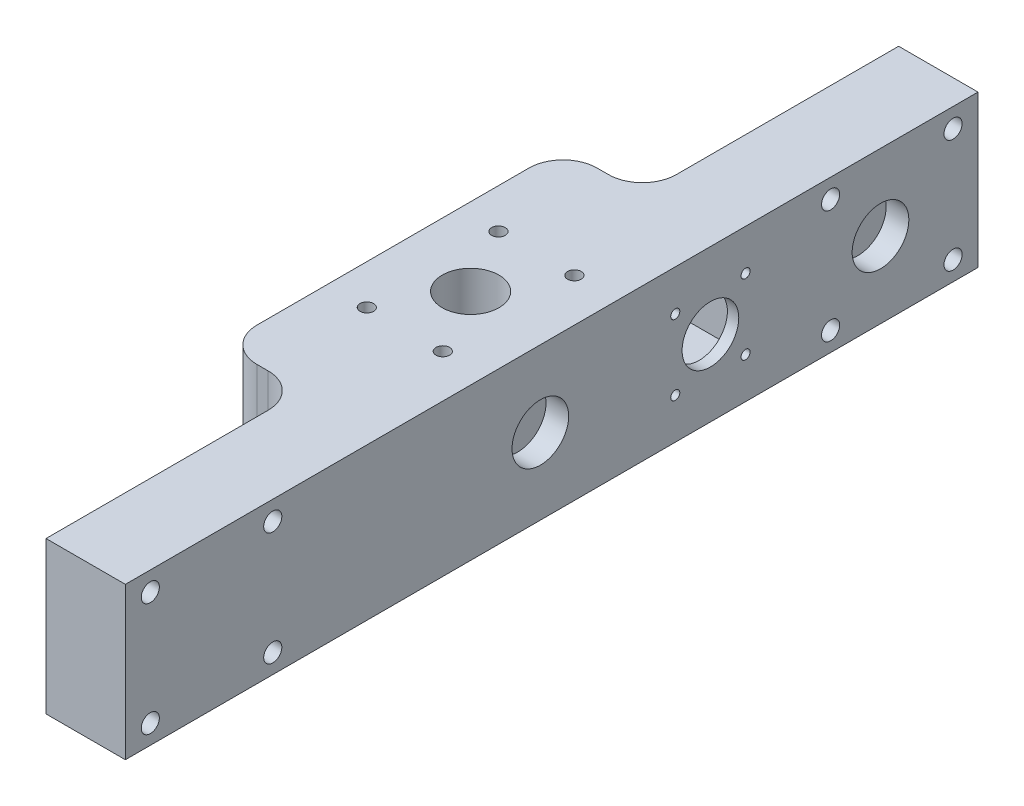
SolidWorks part; units mm, degrees
material "6061-T6 (SS)"
ref_plane "Front" through (0, 0, 0) normal (0, 0, 1) x (1, 0, 0)
ref_plane "Top" through (0, 0, 0) normal (0, 1, 0) x (1, 0, 0)
ref_plane "Right" through (0, 0, 0) normal (1, 0, 0) x (0, 0, -1)
sketch "Sketch1" plane through (0, 0, 0) normal (0, 1, 0) x (1, 0, 0)
  line L0 (0.75, -188) -> (35.75, -188)
  line L1 (0.75, -188) -> (0.75, -75)
  line L2 (0.75, 188) -> (35.75, 188)
  line L3 (35.75, -188) -> (35.75, 188)
  line L4 (-34.25, 75) -> (0.75, 75)
  line L5 (-34.25, 75) -> (-34.25, -75)
  line L6 (-34.25, -75) -> (0.75, -75)
  line L7 (-34.25, 0) -> (0, 0) construction
  line L8 (0.75, 75) -> (0.75, 188)
  line L9 (-16.75, -29.0119) -> (16.75, -29.0119) construction
  line L10 (-16.75, -29.0119) -> (-16.75, 29.0119) construction
  line L11 (-16.75, 29.0119) -> (16.75, 29.0119) construction
  line L12 (16.75, -29.0119) -> (16.75, 29.0119) construction
  line L13 (-16.75, -29.0119) -> (16.75, 29.0119) construction
  line L14 (-16.75, 29.0119) -> (16.75, -29.0119) construction
  circle A0 centre (0, 0) radius 12.5
  circle A1 centre (-16.75, -29.0119) radius 3
  circle A2 centre (16.75, -29.0119) radius 3
  circle A3 centre (16.75, 29.0119) radius 3
  circle A4 centre (-16.75, 29.0119) radius 3
  point P10 (0, 0)
  dimension "D8" = 25
  dimension "D11" = 6
  dimension "D1" = 35
  dimension "D2" = 35
  dimension "D3" = 150
  dimension "D4" = 70
  dimension "D5" = 34.25
  dimension "D6" = 376
  dimension "D7" = 188
  dimension "D9" = 58.0237
  dimension "D10" = 33.5
extrude "Boss-Extrude1" add sketch "Sketch1" along normal blind 67
sketch "Sketch2" plane through (35.75, 0, 0) normal (1, 0, 0) x (0, 0, -1)
  line L0 (-177, 8.5) -> (-123, 8.5) construction
  line L1 (-177, 8.5) -> (-177, 58.5) construction
  line L2 (-177, 58.5) -> (-123, 58.5) construction
  line L3 (-123, 8.5) -> (-123, 58.5) construction
  line L4 (-112, 67) -> (-188, 67) construction
  line L5 (-112, 67) -> (-112, 0) construction
  line L6 (-112, 0) -> (-188, 0) construction
  line L7 (-188, 67) -> (-188, 0) construction
  line L8 (-112, 67) -> (-188, 0) construction
  line L9 (-112, 0) -> (-188, 67) construction
  line L10 (-177, 8.5) -> (-123, 58.5) construction
  line L11 (-177, 58.5) -> (-123, 8.5) construction
  line L12 (-188, 0) -> (188, 0) construction
  line L13 (-188, 67) -> (-188, 0) construction
  line L14 (0, 0) -> (0, 67) construction
  line L15 (-188, 67) -> (188, 67) construction
  circle A0 centre (-177, 58.5) radius 4
  circle A1 centre (-123, 58.5) radius 4
  circle A2 centre (-177, 8.5) radius 4
  circle A3 centre (-123, 8.5) radius 4
  circle A4 centre (177, 58.5) radius 4
  circle A5 centre (177, 8.5) radius 4
  circle A6 centre (123, 8.5) radius 4
  circle A7 centre (123, 58.5) radius 4
  point P4 (-150, 33.5)
  point P9 (-150, 33.5)
  point P32 (0, 33.5)
  dimension "D5" = 8
  dimension "D1" = 50
  dimension "D2" = 54
  dimension "D3" = 76
  dimension "D4" = 67
extrude "Cut-Extrude1" cut sketch "Sketch2" against normal through all
fillet "Fillet1" radius 15 4 edges at (-34.25, 33.5, 75) (-34.25, 33.5, -75) (0.75, 33.5, -75) (0.75, 33.5, 75)
sketch "Sketch3" plane through (35.75, 0, 0) normal (1, 0, 0) x (0, 0, -1)
  line L0 (54.5, 18) -> (85.5, 18) construction
  line L1 (92.5, 11) -> (47.5, 11)
  line L2 (92.5, 11) -> (92.5, 56)
  line L3 (92.5, 56) -> (47.5, 56)
  line L4 (47.5, 11) -> (47.5, 56)
  line L5 (92.5, 11) -> (47.5, 56) construction
  line L6 (92.5, 56) -> (47.5, 11) construction
  line L12 (54.5, 18) -> (54.5, 49) construction
  line L13 (54.5, 49) -> (85.5, 49) construction
  line L14 (85.5, 18) -> (85.5, 49) construction
  line L15 (54.5, 18) -> (85.5, 49) construction
  line L16 (54.5, 49) -> (85.5, 18) construction
  line L17 (0, 0) -> (0, 67) construction
  line L18 (-188, 67) -> (188, 67) construction
  line L19 (0, 33.5) -> (70, 33.5) construction
  line L20 (-5, 33.5) -> (145, 33.5) construction
  circle A0 centre (54.5, 49) radius 2
  circle A1 centre (54.5, 18) radius 2
  circle A2 centre (85.5, 18) radius 2
  circle A3 centre (85.5, 49) radius 2
  circle A4 centre (-5, 33.5) radius 12.5
  circle A5 centre (145, 33.5) radius 12.5
  circle A6 centre (70, 33.5) radius 12.5
  point P0 (70, 33.5)
  point P5 (70, 33.5)
  point P6 (70, 33.5)
  point P25 (70, 33.5)
  dimension "D4" = 4
  dimension "D5" = 70
  dimension "D7" = 25
  dimension "D8" = 25
  dimension "D1" = 31
  dimension "D2" = 31
  dimension "D3" = 45
  dimension "D6" = 150
extrude "Cut-Extrude3" cut sketch "Sketch3" against normal up to surface (70 mm away) from offset 5 contours L4 L1 L2 L3 A3 A2 A1 A0 region at (35.75, 11.6364, -70) up to face at (-34.25, 33.5, 0) offset against normal yes
extrude "Cut-Extrude4" cut sketch "Sketch3<2>" against normal through all contours A0 | A3 | A2 | A1 | A6 region at (35.75, 49, -54.5) region at (35.75, 18, -54.5) region at (35.75, 18, -85.5) region at (35.75, 49, -85.5) region at (35.75, 33.5, -70)
sketch "Sketch3<2>" plane through (35.75, 0, 0) normal (1, 0, 0) x (0, 0, -1) same geometry as "Sketch3"
extrude "Cut-Extrude5" cut sketch "Sketch3<4>" against normal blind 10 contours A4 | A5 region at (35.75, 33.5, 5) region at (35.75, 33.5, -145)
sketch "Sketch3<4>" plane through (35.75, 0, 0) normal (1, 0, 0) x (0, 0, -1) same geometry as "Sketch3"
